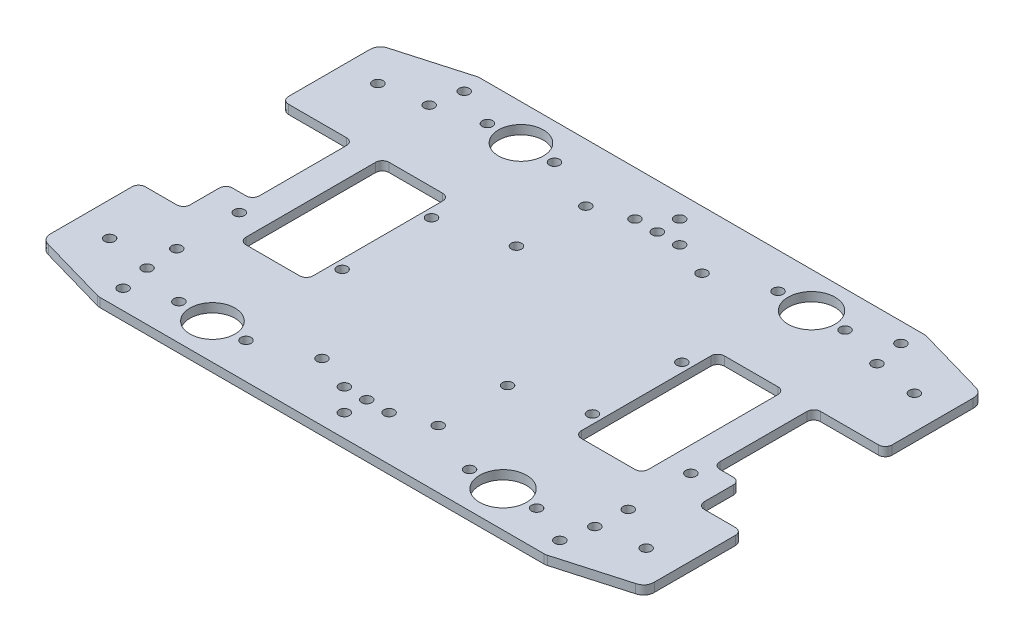
SolidWorks part; units mm, degrees
ref_plane "Plan de face" through (0, 0, 0) normal (0, 0, 1) x (1, 0, 0)
ref_plane "Plan de dessus" through (0, 0, 0) normal (0, 1, 0) x (1, 0, 0)
ref_plane "Plan de droite" through (0, 0, 0) normal (1, 0, 0) x (0, 0, -1)
sketch "Esquisse1" plane through (0, 0, 0) normal (0, 1, 0) x (1, 0, 0)
  line L0 (0, 0) -> (135, 0) construction
  line L1 (0, 0) -> (-135, 0) construction
  line L2 (-135, 0) -> (-135, -75)
  line L3 (-135, -85) -> (135, -85) construction
  line L4 (135, 0) -> (135, 75)
  line L5 (0, 85) -> (0, -85) construction
  line L6 (135, 85) -> (-135, 85) construction
  line L24 (0, -85) -> (-100, -85)
  line L26 (0, -85) -> (100, -85)
  line L28 (135, 0) -> (135, -75)
  line L31 (0, 85) -> (-100, 85)
  line L32 (0, 85) -> (100, 85)
  line L34 (-135, 0) -> (-135, 75)
  line L35 (-135, -75) -> (-100, -85)
  line L37 (-135, 75) -> (-100, 85)
  line L38 (100, 85) -> (135, 75)
  line L39 (100, -85) -> (135, -75)
  dimension "D1" = 270
  dimension "D2" = 200
  dimension "D4" = 170
extrude "Boss.-Extru.1" add sketch "Esquisse1" along normal blind 4
sketch "Esquisse3" plane through (0, 4, 0) normal (0, 1, 0) x (1, 0, 0)
  line L0 (-135, 32) -> (-135, -32)
  line L2 (-135, 0) -> (0, 0) construction
  line L8 (-135, -32) -> (-115, -32)
  line L9 (-115, -32) -> (-115, 32)
  line L10 (-115, 32) -> (-135, 32)
extrude "Enlèv. mat.-Extru.1" cut sketch "Esquisse3" against normal up to next
mirror "Symétrie1" about plane through (0, 0, 0) normal (1, 0, 0) of "Enlèv. mat.-Extru.1"
fillet "Congé1" radius 3 8 edges at (115, 2, -32) (115, 2, 32) (-115, 2, 32) (-115, 2, -32) (135, 2, -32) (135, 2, 32) (-135, 2, 32) (-135, 2, -32)
sketch "Esquisse8" plane through (0, 4, 0) normal (0, 1, 0) x (1, 0, 0)
  line L0 (-115, 0) -> (-90, 0) construction
  line L1 (-115, -29) -> (-115, 29) construction
  line L2 (-90, 0) -> (-90, 32)
  line L3 (-90, 32) -> (-60, 32)
  line L4 (-60, 32) -> (-60, -32)
  line L5 (-60, -32) -> (-90, -32)
  line L6 (-90, -32) -> (-90, 0)
extrude "Enlèv. mat.-Extru.2" cut sketch "Esquisse8" against normal up to next
mirror "Symétrie2" about plane through (0, 0, 0) normal (1, 0, 0) of "Enlèv. mat.-Extru.2"
fillet "Congé2" radius 3 8 edges at (90, 2, 32) (60, 2, 32) (60, 2, -32) (90, 2, -32) (-60, 2, -32) (-60, 2, 32) (-90, 2, 32) (-90, 2, -32)
sketch "Esquisse10" plane through (0, 4, 0) normal (0, 1, 0) x (1, 0, 0)
  line L0 (0, 0) -> (0, -85) construction
  line L1 (-100, -85) -> (100, -85) construction
  line L2 (0, -85) -> (-65, -85) construction
  line L3 (0, -85) -> (65, -85) construction
  line L4 (65, -85) -> (65, -69) construction
  line L5 (-65, -85) -> (-65, -69) construction
  line L6 (-65, -69) -> (-50, -69) construction
  line L7 (-65, -69) -> (-80, -69) construction
  line L8 (65, -69) -> (80, -69) construction
  line L9 (65, -69) -> (50, -69) construction
  circle A0 centre (-65, -69) radius 10.075
  circle A1 centre (65, -69) radius 10.5
  circle A2 centre (80, -69) radius 2.3
  circle A3 centre (50, -69) radius 2.3
  circle A4 centre (-50, -69) radius 2.3
  circle A5 centre (-80, -69) radius 2.3
  dimension "D1" = 20.15
  dimension "D2" = 16
extrude "Enlèv. mat.-Extru.3" cut sketch "Esquisse10" against normal up to next
mirror "Symétrie3" about plane through (0, 0, 0) normal (0, 0, 1) of "Enlèv. mat.-Extru.3"
sketch "Esquisse11" plane through (0, 4, 0) normal (0, 1, 0) x (1, 0, 0)
  line L0 (-60, 0) -> (-60, 24) construction
  line L1 (-60, -29) -> (-60, 29) construction
  line L2 (-60, 24) -> (-52, 24) construction
  line L3 (-52, 24) -> (-52, -24) construction
  line L4 (-52, -24) -> (-60, -24) construction
  line L5 (-60, -24) -> (-60, -16) construction
  line L6 (-60, -16) -> (-52, -24) construction
  line L7 (-60, 24) -> (-60, 16) construction
  line L8 (-60, 16) -> (-52, 24) construction
  circle A10 centre (-56, 20) radius 2.3
  circle A11 centre (-56, -20) radius 2.3
extrude "Enlèv. mat.-Extru.4" cut sketch "Esquisse11" against normal up to next
mirror "Symétrie4" about plane through (0, 0, 0) normal (1, 0, 0) of "Enlèv. mat.-Extru.4"
sketch "Esquisse14" plane through (0, 4, 0) normal (0, 1, 0) x (1, 0, 0)
  line L0 (-60, 0) -> (60, 0) construction
  line L1 (-60, -29) -> (-60, 29) construction
  line L2 (60, -29) -> (60, 29) construction
  line L3 (-60, 0) -> (-60, 32) construction
  line L4 (-60, 32) -> (-52, 32) construction
  line L5 (-52, 32) -> (-30, 32) construction
  line L6 (-30, 32) -> (-22, 32) construction
  line L7 (-22, 32) -> (-22, 24) construction
  line L8 (-22, 32) -> (-22, 63) construction
  line L9 (-22, 63) -> (-30, 63) construction
  line L10 (-30, 63) -> (-30, 55) construction
  line L11 (-30, 55) -> (-22, 63) construction
  line L12 (-22, 24) -> (-30, 32) construction
  line L13 (-22, 24) -> (-22, -63) construction
  line L14 (-22, -63) -> (-30, -63) construction
  line L15 (-30, -63) -> (-30, -55) construction
  line L16 (-30, -55) -> (-22, -63) construction
  line L17 (60, 0) -> (60, -32) construction
  line L18 (60, -32) -> (22, -32) construction
  line L19 (22, -32) -> (22, -63) construction
  line L20 (22, -63) -> (30, -63) construction
  line L21 (30, -63) -> (30, -55) construction
  line L22 (30, -55) -> (22, -63) construction
  line L23 (22, -32) -> (22, -24) construction
  line L24 (22, -24) -> (30, -24) construction
  line L25 (30, -24) -> (22, -32) construction
  line L26 (22, -24) -> (22, 63) construction
  line L27 (22, 63) -> (30, 63) construction
  line L28 (30, 63) -> (30, 55) construction
  line L29 (30, 55) -> (22, 63) construction
  circle A0 centre (-26, 59) radius 2.3
  circle A1 centre (-26, 28) radius 2.3
  circle A2 centre (-26, -59) radius 2.3
  circle A3 centre (26, 59) radius 2.3
  circle A4 centre (26, -28) radius 2.3
  circle A5 centre (26, -59) radius 2.3
extrude "Enlèv. mat.-Extru.5" cut sketch "Esquisse14" against normal up to next
sketch "Esquisse15" plane through (0, 4, 0) normal (0, 1, 0) x (1, 0, 0)
  line L0 (-135, 60) -> (-135, 75)
  line L1 (-135, 60) -> (-120, 60) construction
  line L2 (-135, -60) -> (-120, -60) construction
  line L4 (-135, -60) -> (-135, -75)
  line L5 (-100, 85) -> (-135, 75) construction
  line L6 (-135, 75) -> (-135, 35) construction
  circle A0 centre (-120, 60) radius 2.3
  circle A1 centre (-120, -60) radius 2.3
extrude "Enlèv. mat.-Extru.6" cut sketch "Esquisse15" against normal up to next contours A1 | A0 region at (-120, 4, 60)
mirror "Symétrie5" about plane through (0, 0, 0) normal (1, 0, 0) of "Enlèv. mat.-Extru.6"
sketch "Esquisse17" plane through (0, 4, 0) normal (0, 1, 0) x (1, 0, 0)
  line L0 (0, -85) -> (0, -71) construction
  line L1 (-100, -85) -> (100, -85) construction
  line L2 (0, 85) -> (0, 71) construction
  line L3 (100, 85) -> (-100, 85) construction
  circle A0 centre (0, -71) radius 2.3
  circle A1 centre (0, 71) radius 2.3
  circle A2 centre (10, 71) radius 2.3
  circle A3 centre (10, -71) radius 2.3
  circle A4 centre (-10, 71) radius 2.3
  circle A5 centre (-10, -71) radius 2.3
  dimension "D1" = 2
sketch "Esquisse18" plane through (0, 4, 0) normal (0, 1, 0) x (1, 0, 0)
  line L0 (-135, -75) -> (-135, -32) construction
  line L1 (-135, -32) -> (-105, -32) construction
  line L2 (-105, -32) -> (-97, -32) construction
  line L3 (-97, -32) -> (-97, -40) construction
  line L4 (-97, -40) -> (-105, -32) construction
  line L5 (-97, -40) -> (-97, -60) construction
  line L6 (-97, -60) -> (-105, -60) construction
  line L7 (-105, -60) -> (-105, -68) construction
  line L8 (-105, -68) -> (-97, -60) construction
  circle A0 centre (-101, -64) radius 2.3
  circle A1 centre (-101, -36) radius 2.3
fillet "Congé3" radius 5 8 edges at (-135, 2, -75) (-100, 2, -85) (100, 2, -85) (135, 2, -75) (135, 2, 75) (100, 2, 85) (-100, 2, 85) (-135, 2, 75) second distance 5 conic rho 0.5 first distance on face at (-117.5, 2, -80) first distance on face at (0, 2, -85) first distance on face at (117.5, 2, -80) first distance on face at (135, 2, -55) first distance on face at (117.5, 2, 80) first distance on face at (0, 2, 85) first distance on face at (-117.5, 2, 80) first distance on face at (-135, 2, 55)
sketch "Esquisse19" plane through (0, 4, 0) normal (0, 1, 0) x (1, 0, 0)
  line L0 (0, 0) -> (-135, 0) construction
  line L1 (-105, -32) -> (-135, -32) construction
  line L2 (-135, 0) -> (-135, -32) construction
  line L5 (-105, -32) -> (-105, -25) construction
  line L6 (-105, -25) -> (-105, -17) construction
  line L7 (-105, -17) -> (-97, -17) construction
  line L8 (-97, -17) -> (-97, -25) construction
  line L9 (-97, -25) -> (-105, -25) construction
  line L10 (-97, -25) -> (-97, -45) construction
  line L11 (-97, -45) -> (-105, -45) construction
  line L12 (-105, -45) -> (-105, -53) construction
  line L13 (-105, -17) -> (-97, -25) construction
  line L14 (-97, -25) -> (-97, -45) construction
  line L15 (-97, -45) -> (-105, -53) construction
  circle A1 centre (-101, -49) radius 2.3
  circle A2 centre (-101, -21) radius 2.3
extrude "Enlèv. mat.-Extru.9" cut sketch "Esquisse19" against normal up to next and the other way through all
mirror "Symétrie7" about plane through (0, 0, 0) normal (1, 0, 0) of "Enlèv. mat.-Extru.9"
sketch "Esquisse20" plane through (0, 4, 0) normal (0, 1, 0) x (1, 0, 0)
  line L0 (-120, -60) -> (-110, -60) construction
  line L1 (-110, -60) -> (-110, -70) construction
  line L2 (-110, -70) -> (-130, -70) construction
  line L3 (-130, -70) -> (-130, -50) construction
  line L4 (-130, -50) -> (-110, -50) construction
  line L5 (-110, -50) -> (-110, -60) construction
  line L6 (-116.0235, -80.4219) -> (-114.6499, -75.6142) construction
  line L7 (-131.3736, -76.0361) -> (-100.6733, -84.8076) construction
  line L8 (-114.6499, -75.6142) -> (-108.8807, -77.2626) construction
  line L9 (-104.4852, -61.8782) -> (-95.8315, -64.3507) construction
  line L10 (-103.3863, -58.0321) -> (-88.9634, -62.1529) construction
  line L11 (-88.9634, -62.1529) -> (-94.4579, -81.3834) construction
  line L12 (-94.4579, -81.3834) -> (-108.8807, -77.2626) construction
  line L13 (-103.3863, -58.0321) -> (-104.4852, -61.8782) construction
  line L14 (0, -55) -> (0, 55) construction
  line L15 (-94.4579, -81.3834) -> (-93.359, -77.5373) construction
  line L16 (-93.359, -77.5373) -> (-102.0127, -75.0648) construction
  line L18 (94.4579, -81.3834) -> (99.2997, -80) construction
  line L19 (94.0626, -80) -> (94.4579, -81.3834) construction
  line L20 (99.2997, -80) -> (94.0626, -80) construction
  line L21 (99.2997, -85) -> (99.2997, -80) construction
  line L22 (87.2469, -85) -> (87.2469, -80) construction
  line L23 (93.359, -77.5373) -> (102.0127, -75.0648) construction
  line L24 (94.4579, -81.3834) -> (93.359, -77.5373) construction
  line L25 (103.3863, -58.0321) -> (104.4852, -61.8782) construction
  line L26 (94.4579, -81.3834) -> (108.8807, -77.2626) construction
  line L27 (88.9634, -62.1529) -> (94.4579, -81.3834) construction
  line L28 (103.3863, -58.0321) -> (88.9634, -62.1529) construction
  line L29 (104.4852, -61.8782) -> (95.8315, -64.3507) construction
  line L30 (114.6499, -75.6142) -> (108.8807, -77.2626) construction
  line L31 (116.0235, -80.4219) -> (114.6499, -75.6142) construction
  line L32 (110, -50) -> (110, -60) construction
  line L33 (130, -50) -> (110, -50) construction
  line L35 (130, -70) -> (130, -50) construction
  line L36 (110, -70) -> (130, -70) construction
  line L37 (110, -60) -> (110, -70) construction
  line L38 (120, -60) -> (110, -60) construction
  line L39 (-55, 0) -> (55, 0) construction
  line L40 (-94.4579, 81.3834) -> (-99.2997, 80) construction
  line L41 (-94.0626, 80) -> (-94.4579, 81.3834) construction
  line L42 (-99.2997, 80) -> (-94.0626, 80) construction
  line L43 (-99.2997, 85) -> (-99.2997, 80) construction
  line L44 (-87.2469, 85) -> (-87.2469, 80) construction
  line L45 (120, 60) -> (110, 60) construction
  line L46 (110, 60) -> (110, 70) construction
  line L47 (110, 70) -> (130, 70) construction
  line L48 (130, 70) -> (130, 50) construction
  line L49 (130, 50) -> (110, 50) construction
  line L50 (110, 50) -> (110, 60) construction
  line L51 (116.0235, 80.4219) -> (114.6499, 75.6142) construction
  line L52 (114.6499, 75.6142) -> (108.8807, 77.2626) construction
  line L53 (104.4852, 61.8782) -> (95.8315, 64.3507) construction
  line L54 (103.3863, 58.0321) -> (88.9634, 62.1529) construction
  line L55 (88.9634, 62.1529) -> (94.4579, 81.3834) construction
  line L56 (94.4579, 81.3834) -> (108.8807, 77.2626) construction
  line L57 (103.3863, 58.0321) -> (104.4852, 61.8782) construction
  line L58 (94.4579, 81.3834) -> (93.359, 77.5373) construction
  line L59 (93.359, 77.5373) -> (102.0127, 75.0648) construction
  line L60 (87.2469, 85) -> (87.2469, 80) construction
  line L61 (99.2997, 85) -> (99.2997, 80) construction
  line L62 (99.2997, 80) -> (94.0626, 80) construction
  line L63 (94.0626, 80) -> (94.4579, 81.3834) construction
  line L64 (94.4579, 81.3834) -> (99.2997, 80) construction
  line L65 (-87.2469, -85) -> (-87.2469, -80) construction
  line L66 (-99.2997, -85) -> (99.2997, -85) construction
  line L67 (-99.2997, -85) -> (-99.2997, -80) construction
  line L68 (-99.2997, -80) -> (-94.0626, -80) construction
  line L69 (-94.0626, -80) -> (-94.4579, -81.3834) construction
  line L70 (-94.4579, -81.3834) -> (-99.2997, -80) construction
  line L71 (-93.359, 77.5373) -> (-102.0127, 75.0648) construction
  line L72 (-94.4579, 81.3834) -> (-93.359, 77.5373) construction
  line L73 (-103.3863, 58.0321) -> (-104.4852, 61.8782) construction
  line L74 (-94.4579, 81.3834) -> (-108.8807, 77.2626) construction
  line L75 (-88.9634, 62.1529) -> (-94.4579, 81.3834) construction
  line L76 (-103.3863, 58.0321) -> (-88.9634, 62.1529) construction
  line L77 (-104.4852, 61.8782) -> (-95.8315, 64.3507) construction
  line L78 (-114.6499, 75.6142) -> (-108.8807, 77.2626) construction
  line L79 (-116.0235, 80.4219) -> (-114.6499, 75.6142) construction
  line L80 (-110, 50) -> (-110, 60) construction
  line L81 (-130, 50) -> (-110, 50) construction
  line L82 (-130, 70) -> (-130, 50) construction
  line L83 (-110, 70) -> (-130, 70) construction
  line L84 (-110, 60) -> (-110, 70) construction
  line L85 (-120, 60) -> (-110, 60) construction
  circle A4 centre (-100.1583, -63.1144) radius 2.3
  circle A5 centre (-97.6858, -76.301) radius 2.3
  circle A12 centre (97.6858, -76.301) radius 2.3
  circle A13 centre (100.1583, -63.1144) radius 2.3
  circle A14 centre (100.1583, 63.1144) radius 2.3
  circle A15 centre (97.6858, 76.301) radius 2.3
  circle A16 centre (-97.6858, 76.301) radius 2.3
  circle A17 centre (-100.1583, 63.1144) radius 2.3
  dimension "D4" = 90
  dimension "D10" = 4
  dimension "D11" = 9
  dimension "D1" = 90
  dimension "D2" = 20
  dimension "D3" = 4
  dimension "D5" = 6
  dimension "D6" = 5
  dimension "D7" = 15
  dimension "D8" = 90
  dimension "D9" = 90
  dimension "D12" = 9
  dimension "D13" = 5.0356
  dimension "D14" = 1.4387
  dimension "D15" = 90
  dimension "D16" = 15
  dimension "D17" = 90
  dimension "D18" = 5.2371
  dimension "D19" = 4.5
  dimension "D20" = 90
extrude "Enlèv. mat.-Extru.10" cut sketch "Esquisse20" against normal up to next
sketch "Esquisse21" plane through (0, 4, 0) normal (0, 1, 0) x (1, 0, 0)
  line L0 (0, -85) -> (0, -80) construction
  line L1 (-99.2997, -85) -> (99.2997, -85) construction
  line L2 (0, -80) -> (18, -80) construction
  line L3 (18, -80) -> (18, -60) construction
  line L4 (18, -60) -> (-18, -60) construction
  line L5 (-18, -60) -> (-18, -80) construction
  line L6 (-18, -80) -> (0, -80) construction
  line L7 (0, -60) -> (0, -65) construction
  line L8 (0, -65) -> (10, -65) construction
  line L9 (0, -65) -> (-10, -65) construction
  line L10 (0, -80) -> (0, -75) construction
  line L11 (-55, 0) -> (55, 0) construction
  line L12 (0, 80) -> (0, 75) construction
  line L13 (0, 65) -> (-10, 65) construction
  line L14 (0, 65) -> (10, 65) construction
  line L15 (0, 60) -> (0, 65) construction
  line L16 (-18, 80) -> (0, 80) construction
  line L17 (-18, 60) -> (-18, 80) construction
  line L18 (18, 60) -> (-18, 60) construction
  line L19 (18, 80) -> (18, 60) construction
  line L20 (0, 80) -> (18, 80) construction
  line L21 (0, 85) -> (0, 80) construction
  circle A0 centre (-10, -65) radius 2.3
  circle A1 centre (10, -65) radius 2.3
  circle A2 centre (0, -75) radius 2.3
  circle A3 centre (0, 75) radius 2.3
  circle A4 centre (10, 65) radius 2.3
  circle A5 centre (-10, 65) radius 2.3
  dimension "D8" = 5
  dimension "D1" = 5
  dimension "D2" = 18
  dimension "D3" = 18
  dimension "D4" = 20
  dimension "D5" = 5
  dimension "D6" = 10
  dimension "D7" = 10
extrude "Enlèv. mat.-Extru.11" cut sketch "Esquisse21" against normal up to next
sketch "Esquisse22" plane through (0, 4, 0) normal (0, 1, 0) x (1, 0, 0)
  line L4 (-118, -13) -> (-118, 32)
  line L5 (-118, 32) -> (-103, 32)
  line L6 (-103, 32) -> (-103, -13)
  line L7 (-103, -13) -> (-118, -13)
  line L8 (-118, -13) -> (-135, -13) construction
  line L9 (-135, -13) -> (-135, 32) construction
  dimension "D1" = 17
  dimension "D2" = 45
  dimension "D3" = 15
extrude "Enlèv. mat.-Extru.12" cut sketch "Esquisse22" against normal blind 6
mirror "Symétrie10" about plane through (0, 0, 0) normal (1, 0, 0) of "Enlèv. mat.-Extru.12"
fillet "Congé5" radius 3 6 edges at (-115, 2, 13) (-103, 2, 13) (-103, 2, -32) (103, 2, -32) (103, 2, 13) (115, 2, 13)
sketch "Esquisse23" plane through (0, 4, 0) normal (0, 1, 0) x (1, 0, 0)
  line L0 (0, -85) -> (0, -65) construction
  line L3 (-99.2997, -85) -> (99.2997, -85) construction
  line L4 (-55, 0) -> (55, 0) construction
  circle A2 centre (0, -65) radius 2.3
  circle A3 centre (0, 65) radius 2.3
extrude "Enlèv. mat.-Extru.14" cut sketch "Esquisse23" against normal through all
